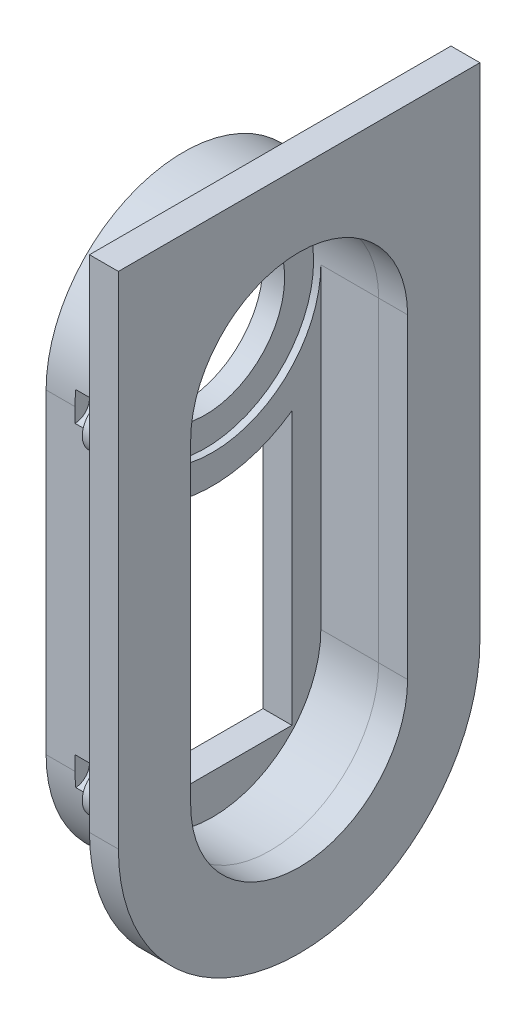
SolidWorks part; units mm, degrees
ref_plane "Front Plane" through (0, 0, 0) normal (0, 0, 1) x (1, 0, 0)
ref_plane "Top Plane" through (0, 0, 0) normal (0, 1, 0) x (1, 0, 0)
ref_plane "Right Plane" through (0, 0, 0) normal (1, 0, 0) x (0, 0, -1)
sketch "Sketch1" plane through (0, 0, 0) normal (1, 0, 0) x (0, 0, -1)
  line L9 (-47.5, 0) -> (-47.5, -100) construction
  line L10 (-27.5, 0) -> (-27.5, -80) construction
  line L11 (27.5, 0) -> (27.5, -80) construction
  line L12 (47.5, 0) -> (47.5, -100) construction
  line L13 (-47.5, -100) -> (47.5, -100) construction
  line L14 (-27.5, -80) -> (27.5, -80) construction
  line L15 (47.5, 0) -> (47.5, -109.2083)
  line L16 (27.5, -38.7298) -> (27.5, -132.9168)
  line L17 (-47.5, -109.2083) -> (-47.5, 0)
  line L18 (-27.5, -38.7298) -> (-27.5, -132.9168)
  line L19 (-27.5, -132.9168) -> (27.5, -132.9168)
  arc A0 (27.5, 0) -> (-27.5, 0) centre (0, 0) ccw
  arc A1 (47.5, 0) -> (-47.5, 0) centre (0, 0) ccw
  arc A3 (47.5, 0) -> (-47.5, 0) centre (0, 0) ccw
  circle A4 centre (0, 0) radius 27.5
  arc A5 (-27.5, -38.7298) -> (27.5, -38.7298) centre (0, 0) ccw
  arc A6 (-47.5, -109.2083) -> (47.5, -109.2083) centre (0, -109.2083) ccw
  dimension "D1" = 55
  dimension "D2" = 47.5
  dimension "D4" = 20
extrude "Boss-Extrude1" add sketch "Sketch1" along normal blind 10 contours L17 L15 A1 A4 A0 L18 A5 L16 L19 region at (0, -54.6042, -45.2478)
sketch "Sketch2" plane through (10, 0, 0) normal (1, 0, 0) x (0, 0, -1)
  line L8 (-47.5, 0) -> (-47.5, -109.2083)
  line L9 (47.5, -109.2083) -> (47.5, 0)
  line L10 (-47.5, 0) -> (-47.5, -109.2083)
  line L11 (47.5, -109.2083) -> (47.5, 0)
  line L12 (37.5, -109.2083) -> (37.5, 0)
  line L13 (-37.5, 0) -> (-37.5, -109.2083)
  arc A7 (-47.5, -109.2083) -> (47.5, -109.2083) centre (0, -109.2083) ccw
  arc A8 (47.5, 0) -> (-47.5, 0) centre (0, 0) ccw
  arc A10 (47.5, 0) -> (-47.5, 0) centre (0, 0) ccw
  arc A11 (37.5, 0) -> (-37.5, 0) centre (0, 0) ccw
  arc A12 (-37.5, -109.2083) -> (37.5, -109.2083) centre (0, -109.2083) ccw
  arc A14 (-47.5, -109.2083) -> (47.5, -109.2083) centre (0, -109.2083) ccw
  dimension "D2" = 10
  dimension "D1" = 0
extrude "Boss-Extrude2" add sketch "Sketch2" along normal blind 30 contours L10 A14 L11 A10 | L13 A12 L12 A11
ref_plane "Plane1" through (0, 47.5, 0) normal (0, 1, 0) x (1, 0, 0)
sketch "Sketch4" plane through (40, 0, 0) normal (1, 0, 0) x (0, 0, -1)
  line L4 (-47.5, 0) -> (-47.5, -109.2083)
  line L8 (47.5, -109.2083) -> (47.5, 0)
  line L11 (47.5, -109.2083) -> (47.5, 0)
  line L14 (-47.5, -109.2083) -> (-47.5, 0)
  line L17 (62.5, 63) -> (-62.5, 63)
  line L24 (62.5, -110) -> (62.5, 63)
  line L31 (-62.5, 63) -> (-62.5, -110)
  line L32 (62.5, 63) -> (-62.5, 63)
  line L33 (62.5, -110) -> (62.5, 63)
  line L34 (-62.5, 63) -> (-62.5, -110)
  arc A4 (47.5, 0) -> (-47.5, 0) centre (0, 0) ccw
  arc A16 (-47.5, -109.2083) -> (47.5, -109.2083) centre (0, -109.2083) ccw
  arc A18 (47.5, 0) -> (-47.5, 0) centre (0, 0) ccw
  circle A21 centre (0, 0) radius 42.5
  arc A25 (-47.5, -109.2083) -> (47.5, -109.2083) centre (0, -109.2083) ccw
  arc A26 (-62.5, -110) -> (62.5, -110) centre (0, -110) ccw
  arc A27 (-62.5, -110) -> (62.5, -110) centre (0, -110) ccw
  line M46 (47.5, -109.2083) -> (47.5, 0)
  arc M47 (47.5, 0) -> (-47.5, 0) centre (0, 0) ccw
  line M48 (-47.5, 0) -> (-47.5, -109.2083)
  dimension "D2" = 0
  dimension "D1" = 0
extrude "Boss-Extrude4" add sketch "Sketch4" against normal blind 10 contours M47 M46 M48 region at (40, -23.5, -59.8338)
sketch "Sketch7" plane through (10, 0, 0) normal (1, 0, 0) x (0, 0, -1)
  arc A4 (37.5, 0) -> (-37.5, 0) centre (0, 0) ccw construction
  circle A5 centre (0, 0) radius 37.5
  circle A7 centre (0, 0) radius 27.25
  circle A8 centre (0, 0) radius 27.25
  arc A9 (37.5, 0) -> (-37.5, 0) centre (0, 0) ccw
  dimension "D2" = 0
extrude "Cut-Extrude1" cut sketch "Sketch7" against normal blind 2.5 contours A5 A8 region at (10, -36.4393, 0)
ref_plane "Plane2" through (40.0028, 0, 0) normal (-1, 0, 0) x (0, 0, 1)
sketch "Sketch8" plane through (30, 0, 0) normal (-1, 0, 0) x (0, 0, 1)
  line L2 (47.5, -109.2083) -> (47.5, 0)
  line L3 (-47.5, 0) -> (-47.5, -109.2083)
  line L4 (47.5, -109.2083) -> (47.5, 0)
  line L5 (-47.5, 0) -> (-47.5, -109.2083)
  circle A0 centre (-47.5, -109.2083) radius 7.5
  circle A1 centre (-47.5, 0) radius 7.5
  arc A2 (47.5, 0) -> (-47.5, 0) centre (0, 0) ccw
  arc A3 (-47.5, -109.2083) -> (47.5, -109.2083) centre (0, -109.2083) ccw
  arc A4 (47.5, 0) -> (-47.5, 0) centre (0, 0) ccw
  arc A5 (-47.5, -109.2083) -> (47.5, -109.2083) centre (0, -109.2083) ccw
  circle A6 centre (47.5, 0) radius 7.5
  circle A7 centre (47.5, -109.2083) radius 7.5
  circle A8 centre (0, -156.7083) radius 7.5
  arc M6 (-47.5, 0) -> (47.5, 0) centre (0, 0) cw
  line M7 (47.5, 0) -> (47.5, -109.2083)
  arc M8 (47.5, -109.2083) -> (-47.5, -109.2083) centre (0, -109.2083) cw
  line M9 (-47.5, -109.2083) -> (-47.5, 0)
  dimension "D2" = 15
  dimension "D3" = 15
  dimension "D4" = 15
  dimension "D5" = 15
  dimension "D6" = 15
  dimension "D1" = 0
extrude "Boss-Extrude5" add sketch "Sketch8" along normal blind 10 contours A0 M9 M8 | A8 M8 | A7 M8 M7 | A6 A4 M7 | A1 M6 M9 | A4 region at (30, -109.301, 50.6277) region at (30, 0.0927, 50.6277) region at (30, -159.7824, 0) region at (30, 0.0927, -50.6277) region at (30, -109.301, -50.6277)
sketch "Sketch9" plane through (20, 0, 0) normal (-1, 0, 0) x (0, 0, 1)
  circle A0 centre (0, -156.7083) radius 5
  arc A1 (-7.4766, -156.1162) -> (7.4766, -156.1162) centre (0, -109.2083) ccw construction
  circle A2 centre (47.5, -109.2083) radius 5
  circle A3 centre (47.5, 0) radius 5
  arc A4 (47.5, 0) -> (46.9079, 7.4766) centre (0, 0) ccw construction
  circle A7 centre (-47.5, 0) radius 5
  circle A8 centre (-47.5, -109.2083) radius 5
  dimension "D1" = 10
extrude "Cut-Extrude2" cut sketch "Sketch9" along normal blind 10
split "Split1" bodies to split 112 resulting bodies 113 114 split by face at (30, -72.9925, 0)
